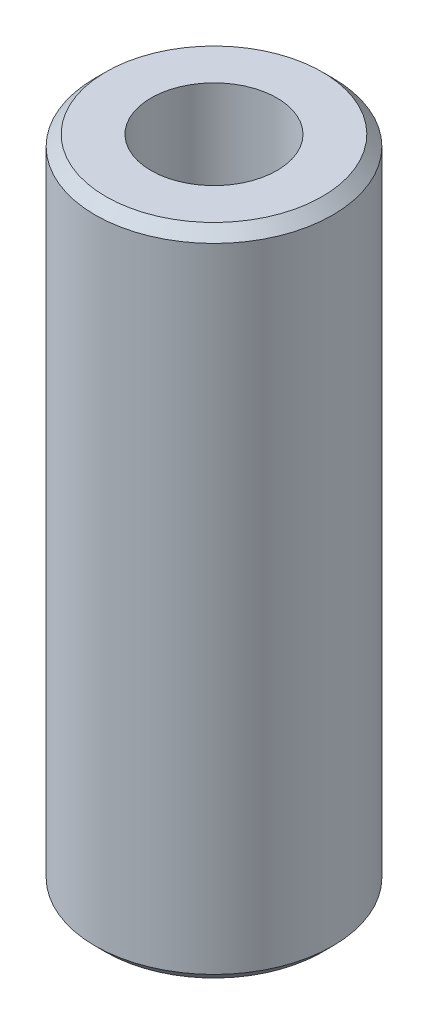
SolidWorks part; units mm, degrees
ref_plane "Front Plane" through (0, 0, 0) normal (0, 0, 1) x (1, 0, 0)
ref_plane "Top Plane" through (0, 0, 0) normal (0, 1, 0) x (1, 0, 0)
ref_plane "Right Plane" through (0, 0, 0) normal (1, 0, 0) x (0, 0, -1)
sketch "Sketch1" plane through (0, 0, 0) normal (0, 1, 0) x (1, 0, 0)
  circle A0 centre (0, 0) radius 45
  dimension "SHAFT_OD" = 90
extrude "Boss-Extrude1" add sketch "Sketch1" along normal blind 248.0287
sketch "Sketch2" plane through (0, 0, 0) normal (0, 1, 0) x (1, 0, 0)
  circle A0 centre (0, 0) radius 23.8628
  dimension "BORE_D" = 47.7255
extrude "Cut-Extrude1" cut sketch "Sketch2" along normal through all
chamfer "Chamfer1" distance 4.033 angle 45 2 edges at (0, 248.0287, 45) (0, 0, 45)
